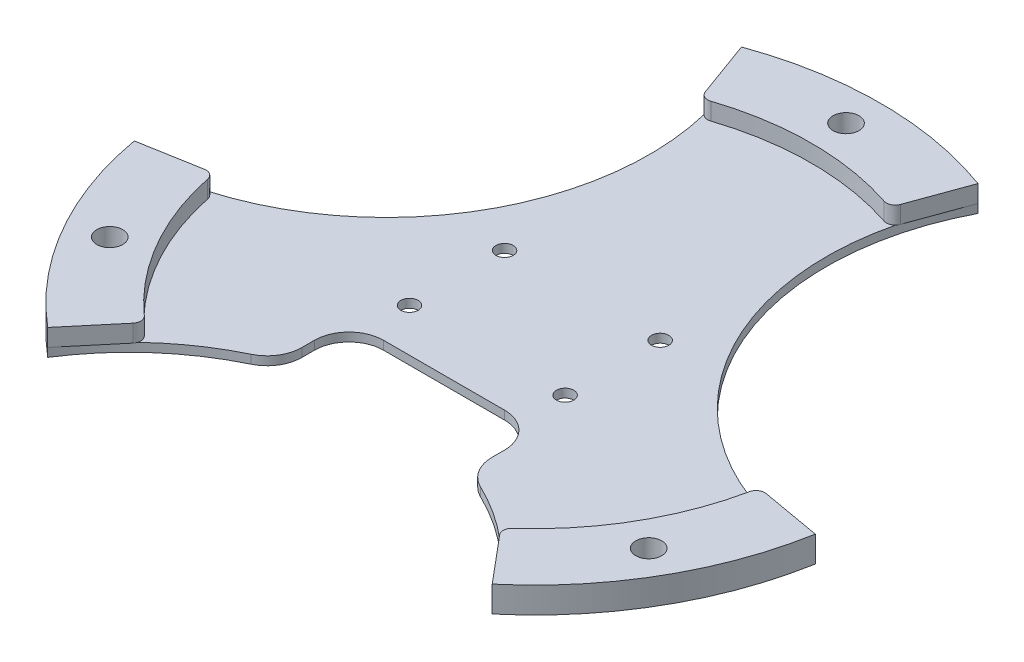
SolidWorks part; units mm, degrees
ref_plane "Front Plane" through (0, 0, 0) normal (0, 0, 1) x (1, 0, 0)
ref_plane "Top Plane" through (0, 0, 0) normal (0, 1, 0) x (1, 0, 0)
ref_plane "Right Plane" through (0, 0, 0) normal (1, 0, 0) x (0, 0, -1)
sketch "Sketch1" plane through (0, 0, 0) normal (0, 1, 0) x (1, 0, 0)
  circle A0 centre (0, 0) radius 40
  dimension "D1" = 80
extrude "Boss-Extrude1" add sketch "Sketch1" along normal blind 1
sketch "Sketch2" plane through (0, 1, 0) normal (0, 1, 0) x (1, 0, 0)
  line L0 (-13.6808, 37.5877) -> (0, 0) construction
  line L1 (0, 0) -> (13.6808, 37.5877) construction
  line L2 (0, -1000) -> (0, 49000) construction
  line L3 (-13.6808, 37.5877) -> (-10.9446, 30.0702)
  line L4 (10.9446, 30.0702) -> (13.6808, 37.5877)
  arc A0 (13.6808, 37.5877) -> (-13.6808, 37.5877) centre (0, 0) ccw
  circle A1 centre (0, 0) radius 40 construction
  arc A2 (10.9446, 30.0702) -> (-10.9446, 30.0702) centre (0, 0) ccw
  circle A3 centre (0, 36) radius 1.5
  dimension "D1" = 8
  dimension "D5" = 3
  dimension "D2" = 20
  dimension "D3" = 20
  dimension "D4" = 36
extrude "Boss-Extrude2" add sketch "Sketch2" along normal blind 2
sketch "Sketch16" plane through (0, 3, 0) normal (0, 1, 0) x (1, 0, 0)
  circle A0 centre (0, 36) radius 1.5
  circle A1 centre (0, 36) radius 1.5 construction
extrude "Cut-Extrude9" cut sketch "Sketch16" against normal through all
pattern_circular "CirPattern1" count 3 over 360 about axis through (0, 1, 0) along (0, -1, 0) of "Boss-Extrude2", "Cut-Extrude9" reverse direction yes
sketch "Sketch5" plane through (0, 1, 0) normal (0, 1, 0) x (1, 0, 0)
  circle A1 centre (40.6986, 23.4973) radius 30.4713
extrude "Cut-Extrude3" cut sketch "Sketch5" against normal through all
pattern_circular "CirPattern2" count 3 over 360 about axis through (0, 1, 0) along (0, -1, 0) of "Cut-Extrude3" reverse direction yes
fillet "Fillet2" radius 1 6 edges at (31.5138, 2, 5.5567) (10.9446, 2, -30.0702) (-10.9446, 2, -30.0702) (20.5692, 2, 24.5134) (-31.5138, 2, 5.5567) (-20.5692, 2, 24.5134)
sketch "Sketch18" plane through (0, 1, 0) normal (0, 1, 0) x (1, 0, 0)
  line L0 (-1000, 0) -> (49000, 0) construction
  line L1 (-9, -5.5) -> (9, -5.5) construction
  line L2 (-9, -5.5) -> (-9, 5.5) construction
  line L3 (-9, 5.5) -> (9, 5.5) construction
  line L4 (9, -5.5) -> (9, 5.5) construction
  line L5 (-9, -5.5) -> (9, 5.5) construction
  line L6 (-9, 5.5) -> (9, -5.5) construction
  circle A0 centre (9, 5.5) radius 1
  circle A1 centre (-9, 5.5) radius 1
  circle A2 centre (9, -5.5) radius 1
  circle A3 centre (-9, -5.5) radius 1
  point P0 (0, 0)
  point P11 (10.1902, 2.7222)
  dimension "D1" = 2
  dimension "D2" = 11
  dimension "D3" = 18
extrude "Cut-Extrude10" cut sketch "Sketch18" against normal through all
sketch "Sketch20" plane through (0, 1, 0) normal (0, 1, 0) x (1, 0, 0)
  line L1 (11, -20.5) -> (-11, -20.5) construction
  line L2 (11, -20.5) -> (11, 7.5) construction
  line L3 (11, 7.5) -> (-11, 7.5) construction
  line L4 (-11, -20.5) -> (-11, 7.5) construction
  line L5 (11, -20.5) -> (-11, 7.5) construction
  line L6 (11, 7.5) -> (-11, -20.5) construction
  line L7 (-11, -20.5) -> (11, -20.5)
  line L8 (-11, -20.5) -> (-11, -10.5)
  line L9 (-11, -10.5) -> (11, -10.5)
  line L10 (11, -20.5) -> (11, -10.5)
  circle A0 centre (9, 5.5) radius 1 construction
  point P0 (0, -6.5)
  dimension "D3" = 2
  dimension "D1" = 22
  dimension "D2" = 28
  dimension "D4" = 10
extrude "Cut-Extrude12" cut sketch "Sketch20" against normal through all
fillet "Fillet3" radius 4 4 edges at (11, 0.5, 18.5781) (11, 0.5, 10.5) (-11, 0.5, 10.5) (-11, 0.5, 18.5781)
